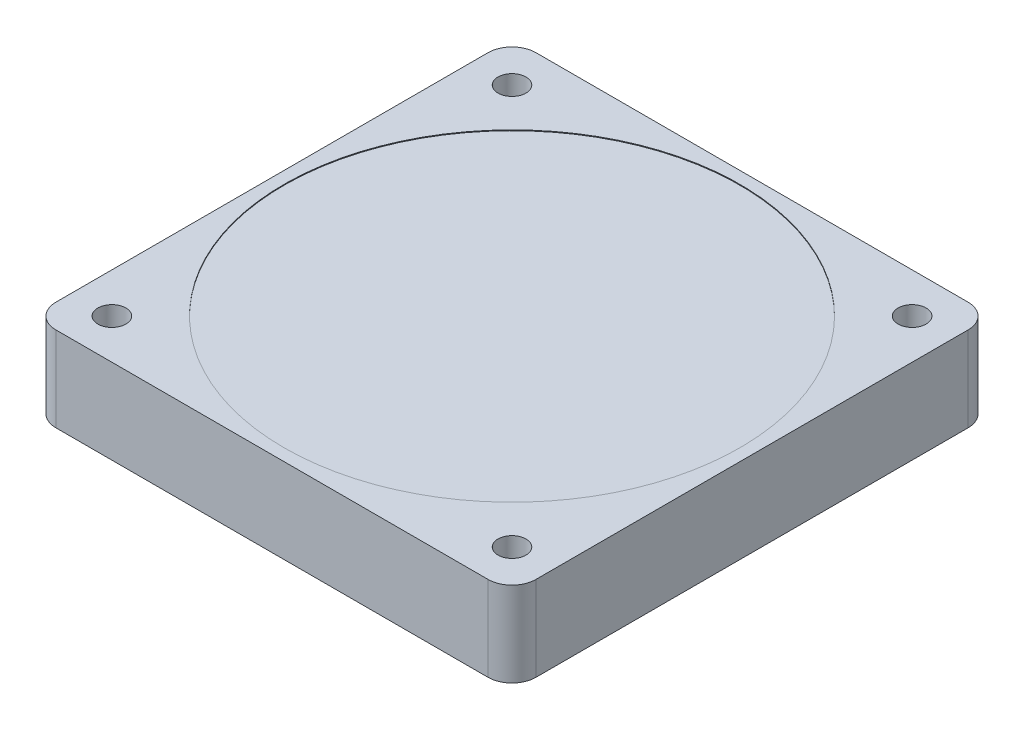
SolidWorks part; units mm, degrees
ref_plane "Front Plane" through (0, 0, 0) normal (0, 0, 1) x (1, 0, 0)
ref_plane "Top Plane" through (0, 0, 0) normal (0, 1, 0) x (1, 0, 0)
ref_plane "Right Plane" through (0, 0, 0) normal (1, 0, 0) x (0, 0, -1)
sketch "Sketch1" plane through (0, 0, 0) normal (0, 1, 0) x (1, 0, 0)
  line L1 (-23.8889, 31.5741) -> (36.1111, 31.5741)
  line L2 (-23.8889, 31.5741) -> (-23.8889, -28.4259)
  line L3 (-23.8889, -28.4259) -> (36.1111, -28.4259)
  line L4 (36.1111, 31.5741) -> (36.1111, -28.4259)
  dimension "D1" = 60
  dimension "D2" = 60
extrude "Boss-Extrude1" add sketch "Sketch1" along normal blind 10.6
fillet "Fillet1" radius 3 4 edges at (36.1111, 5.3, 28.4259) (36.1111, 5.3, -31.5741) (-23.8889, 5.3, -31.5741) (-23.8889, 5.3, 28.4259)
sketch "Sketch2" plane through (0, 10.6, 0) normal (0, 1, 0) x (1, 0, 0)
  line L0 (-18.8889, 26.5741) -> (-23.8889, 26.5741) construction
  line L1 (-23.8889, 28.5741) -> (-23.8889, -25.4259) construction
  line L2 (31.1111, 26.5741) -> (36.1111, 26.5741) construction
  line L3 (36.1111, -25.4259) -> (36.1111, 28.5741) construction
  line L4 (-18.8889, 26.5741) -> (-18.8889, 31.5741) construction
  line L5 (33.1111, 31.5741) -> (-20.8889, 31.5741) construction
  line L6 (-18.8889, -23.4259) -> (-18.8889, -28.4259) construction
  line L7 (-20.8889, -28.4259) -> (33.1111, -28.4259) construction
  circle A0 centre (-18.8889, 26.5741) radius 1.75
  circle A1 centre (31.1111, 26.5741) radius 1.75
  circle A2 centre (31.1111, -23.4259) radius 1.75
  circle A3 centre (-18.8889, -23.4259) radius 1.75
  dimension "D1" = 3.5
  dimension "D2" = 3.5
  dimension "D3" = 3.5
  dimension "D4" = 3.5
  dimension "D5" = 50
  dimension "D6" = 50
extrude "Cut-Extrude1" cut sketch "Sketch2" against normal through all
sketch "Sketch3" plane through (0, 10.6, 0) normal (0, 1, 0) x (1, 0, 0)
  line L0 (-18.8889, 26.5741) -> (31.1111, -23.4259)
  circle A0 centre (6.1111, 1.5741) radius 28.5
  point P6 (11.0036, 5.3901)
  point P7 (6.1111, 1.5741)
  dimension "D1" = 57
extrude "Cut-Extrude2" cut sketch "Sketch3" against normal blind 0.1 contours L0 A0 | L0 A0 region at (14.6641, 10.6, -10.1271) region at (-2.4419, 10.6, 6.9789)
extrude "Cut-Extrude3" cut sketch "Sketch3<3>" along normal blind 0.1 from surface contours L0 A0 | L0 A0 region at (14.6641, 10.6, -10.1271) region at (-2.4419, 10.6, 6.9789) starting at face at (-18.8889, 0, 25.1759)
sketch "Sketch3<3>" plane through (0, 10.6, 0) normal (0, 1, 0) x (1, 0, 0) same geometry as "Sketch3"
